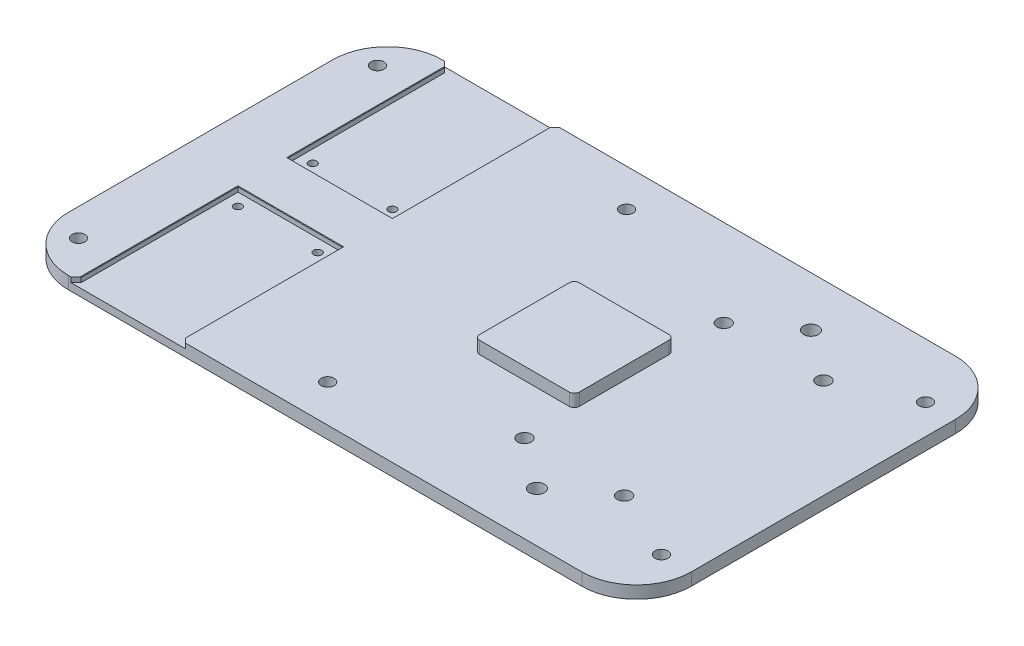
SolidWorks part; units mm, degrees
ref_plane "前视基准面" through (0, 0, 0) normal (0, 0, 1) x (1, 0, 0)
ref_plane "上视基准面" through (0, 0, 0) normal (0, 1, 0) x (1, 0, 0)
ref_plane "右视基准面" through (0, 0, 0) normal (1, 0, 0) x (0, 0, -1)
other "Configuration Table"
sketch "草图1" plane through (0, 0, 0) normal (0, 1, 0) x (1, 0, 0)
  line L0 (103, 75) -> (95, 75)
  line L5 (-125, 53) -> (-125, -53)
  line L6 (-103, -75) -> (55, -75)
  line L7 (125, -53) -> (125, 53)
  line L8 (-1000, 0) -> (49000, 0) construction
  line L9 (55, -75) -> (95, -75)
  line L14 (55, 75) -> (95, 75)
  line L15 (45, -40) -> (85, -40) construction
  line L20 (55, 75) -> (-103, 75)
  line L21 (95, -75) -> (103, -75)
  arc A0 (125, 53) -> (103, 75) centre (103, 53) ccw
  arc A1 (-103, 75) -> (-125, 53) centre (-103, 53) ccw
  arc A2 (-125, -53) -> (-103, -75) centre (-103, -53) ccw
  arc A3 (103, -75) -> (125, -53) centre (103, -53) ccw
  circle A4 centre (-114, 60) radius 2.6
  circle A5 centre (-14, 60) radius 2.6
  circle A6 centre (113, 53) radius 2.6
  circle A7 centre (-114, -60) radius 2.6
  circle A8 centre (-14, -60) radius 2.6
  circle A9 centre (113, -53) radius 2.6
  circle A10 centre (65, -55) radius 3
  circle A11 centre (65, 55) radius 3
  circle A12 centre (45, -40) radius 2.75
  circle A13 centre (85, -40) radius 2.75
  circle A14 centre (85, 40) radius 2.75
  circle A15 centre (45, 40) radius 2.75
  dimension "D3" = 22
  dimension "D4" = 22
  dimension "D5" = 22
  dimension "D6" = 22
  dimension "D9" = 100
  dimension "D10" = 127
  dimension "D11" = 22
  dimension "D12" = 127
  dimension "D13" = 100
  dimension "D14" = 120
  dimension "D15" = 7
  dimension "D16" = 11
  dimension "D17" = 60
  dimension "D18" = 20
  dimension "D19" = 6
  dimension "D20" = 5.5
  dimension "D21" = 5.5
  dimension "D23" = 20
  dimension "D24" = 20
  dimension "D25" = 5.2
  dimension "D1" = 150
  dimension "D2" = 250
  dimension "D7" = 125
  dimension "D8" = 75
  dimension "D22" = 15
extrude "凸台-拉伸1" add sketch "草图1" along normal blind 5
sketch "草图2" plane through (0, 5, 0) normal (0, 1, 0) x (1, 0, 0)
  line L0 (-103, -75) -> (103, -75) construction
  line L1 (-100, -75) -> (-58, -75)
  line L2 (-100, -75) -> (-100, -10)
  line L3 (-100, -10) -> (-58, -10)
  line L4 (-58, -75) -> (-58, -10)
  line L5 (-125, 53) -> (-125, -53) construction
  line L6 (-1000, 0) -> (49000, 0) construction
  line L7 (-58, 75) -> (-58, 10)
  line L8 (-100, 10) -> (-58, 10)
  line L9 (-100, 75) -> (-100, 10)
  line L10 (-100, 75) -> (-58, 75)
  dimension "D1" = 42
  dimension "D2" = 25
  dimension "D3" = 65
extrude "切除-拉伸1" cut sketch "草图2" against normal blind 2
chamfer "倒角1" distance 0.2 angle 45 6 edges at (-58, 5, -42.5) (-79, 5, -10) (-100, 5, -42.5) (-58, 5, 42.5) (-79, 5, 10) (-100, 5, 42.5)
sketch "草图3" plane through (0, 3, 0) normal (0, 1, 0) x (1, 0, 0)
  line L0 (-1000, 0) -> (49000, 0) construction
  line L1 (-100, 10) -> (-58, 10) construction
  line L2 (-58, 10) -> (-58, 75) construction
  line L3 (-100, 75) -> (-100, 10) construction
  circle A0 centre (-95, 15) radius 1.6
  circle A1 centre (-63, 15) radius 1.6
  circle A2 centre (-63, -15) radius 1.6
  circle A3 centre (-95, -15) radius 1.6
  dimension "D1" = 3.2
  dimension "D2" = 3.2
  dimension "D3" = 5
  dimension "D4" = 5
  dimension "D5" = 5
  dimension "D6" = 5
extrude "切除-拉伸2" cut sketch "草图3" against normal blind 3
sketch "草图4" plane through (0, 5, 0) normal (0, 1, 0) x (1, 0, 0)
  line L0 (-1000, 0) -> (49000, 0) construction
  line L1 (0, -1000) -> (0, 49000) construction
  line L3 (5, -20) -> (45, -20)
  line L4 (5, -20) -> (5, 20)
  line L5 (5, 20) -> (45, 20)
  line L6 (45, -20) -> (45, 20)
  line L7 (5, -20) -> (45, 20) construction
  line L8 (5, 20) -> (45, -20) construction
  point P4 (25, 0)
  dimension "D1" = 40
  dimension "D2" = 40
  dimension "D3" = 5
chamfer "倒角2" distance 2 4 edges at (-100, 3.9, -75) (-58, 3.9, -75) (-58, 3.9, 75) (-100, 3.9, 75)
extrude "凸台-拉伸2" add sketch "草图4" along normal blind 5
fillet "圆角3" radius 2 4 edges at (5, 7.5, -20) (45, 7.5, -20) (45, 7.5, 20) (5, 7.5, 20)
